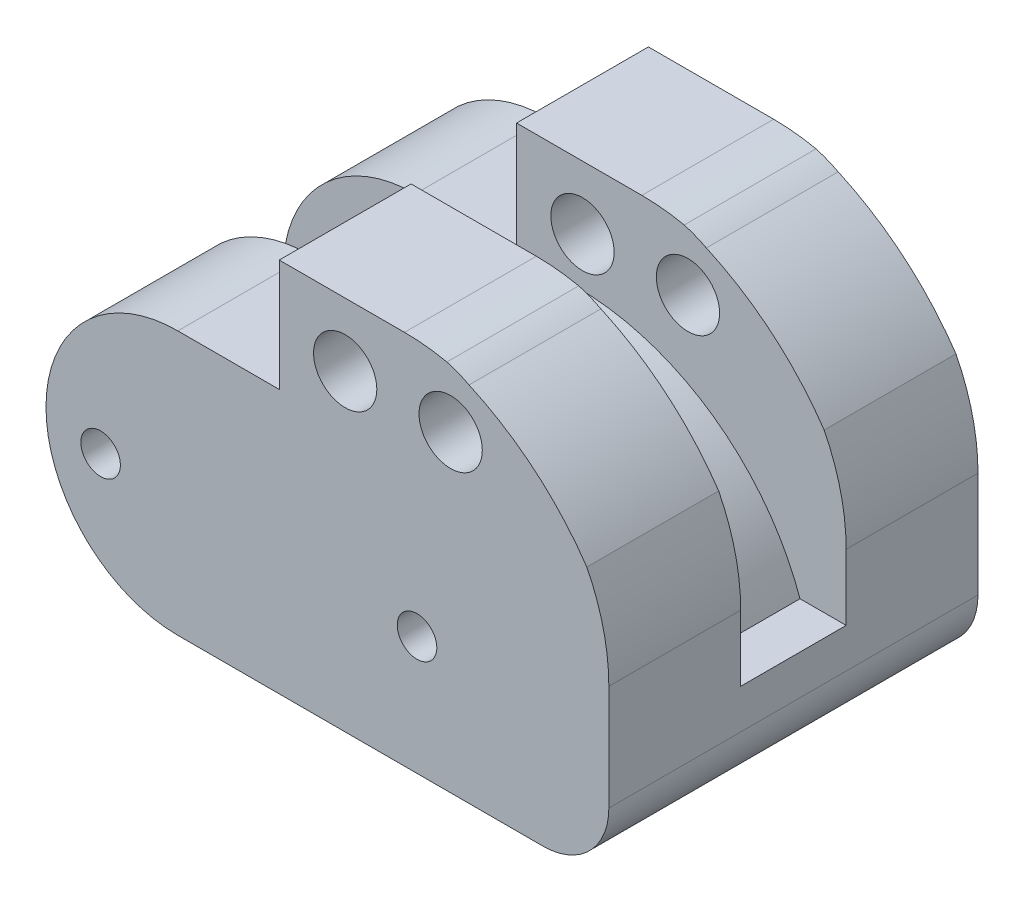
SolidWorks part; units mm, degrees
ref_plane "Alzado" through (0, 0, 0) normal (0, 0, 1) x (1, 0, 0)
ref_plane "Planta" through (0, 0, 0) normal (0, 1, 0) x (1, 0, 0)
ref_plane "Vista lateral" through (0, 0, 0) normal (1, 0, 0) x (0, 0, -1)
sketch "Croquis1" plane through (0, 0, 0) normal (0, 1, 0) x (1, 0, 0)
  line L1 (0, 0) -> (75, 0)
  line L2 (0, 0) -> (0, 28)
  line L3 (0, 28) -> (75, 28)
  line L4 (75, 0) -> (75, 28)
  dimension "D1" = 75
  dimension "D2" = 28
extrude "Saliente-Extruir2" add sketch "Croquis1" along normal blind 20
sketch "Croquis2" plane through (0, 20, 0) normal (0, 1, 0) x (1, 0, 0)
  line L0 (75, 0) -> (75, 28) construction
  line L1 (0, 0) -> (75, 0)
  line L2 (0, 0) -> (0, 10)
  line L3 (0, 10) -> (75, 10)
  line L4 (75, 0) -> (75, 10)
  line L6 (0, 28) -> (75, 28)
  line L7 (0, 28) -> (0, 18)
  line L8 (0, 18) -> (75, 18)
  line L9 (75, 28) -> (75, 18)
  dimension "D1" = 10
  dimension "D2" = 10
extrude "Saliente-Extruir3" add sketch "Croquis2" along normal blind 8.5
sketch "Croquis3" plane through (0, 0, 0) normal (0, 0, 1) x (1, 0, 0)
  line L1 (0, 28.5) -> (75, 28.5) construction
  line L2 (75, 28.5) -> (75, 0) construction
  circle A1 centre (63, 23.7) radius 2.4
  circle A2 centre (55, 23.7) radius 2.4
  dimension "D1" = 12
  dimension "D4" = 4.8
  dimension "D5" = 4.8
  dimension "D7" = 4.8
  dimension "D8" = 4.8
  dimension "D9" = 8
extrude "Cortar-Extruir1" cut sketch "Croquis3" against normal blind 28
sketch "Croquis5" plane through (0, 20, 0) normal (0, 1, 0) x (1, 0, 0)
  line L0 (0, 18) -> (75, 18) construction
  line L1 (75, 10) -> (71.5, 10)
  line L2 (75, 10) -> (75, 18)
  line L3 (75, 18) -> (71.5, 18)
  line L4 (71.5, 10) -> (71.5, 18)
  dimension "D1" = 3.5
extrude "Cortar-Extruir2" cut sketch "Croquis5" against normal blind 12
fillet "Redondeo1" radius 18 1 edges at (71.5, 20, -14)
sketch "Croquis7" plane through (0, 0, -18) normal (0, 0, 1) x (1, 0, 0)
  line L0 (55, 23.7) -> (50, 23.7) construction
  line L1 (50, 28.5) -> (50, 20)
  line L2 (0, 28.5) -> (75, 28.5) construction
  line L3 (0, 20) -> (54.5294, 20) construction
  line L4 (50, 28.5) -> (0, 28.5)
  line L5 (0, 28.5) -> (0, 20)
  line L6 (0, 20) -> (50, 20)
  circle A0 centre (55, 23.7) radius 2.4 construction
  dimension "D1" = 5
extrude "Cortar-Extruir3" cut sketch "Croquis7" against normal blind 9.5 and the other way blind 18.5
sketch "Croquis8" plane through (0, 20, 0) normal (0, 1, 0) x (1, 0, 0)
  line L0 (0, 27.5) -> (0, 0) construction
  line L1 (50, 10) -> (0, 10)
  line L2 (50, 10) -> (50, 19)
  line L3 (50, 19) -> (0, 19)
  line L4 (0, 10) -> (0, 19)
  dimension "D1" = 9
extrude "Cortar-Extruir4" cut sketch "Croquis8" against normal blind 20.5
fillet "Redondeo2" radius 10 2 edges at (0, 20, -5) (0, 20, -23.25)
sketch "Croquis9" plane through (0, 0, -28) normal (0, 0, -1) x (-1, 0, 0)
  line L0 (-75, 28.5) -> (-59.5, 28.5)
  line L1 (-75, 28.5) -> (0, 28.5) construction
  line L3 (-59.5, 28.5) -> (-59.5, 13) construction
  line L4 (-75, 28.5) -> (-75, 0) construction
  line L5 (-75, 28.5) -> (-75, 13)
  arc A0 (-75, 13) -> (-59.5, 28.5) centre (-59.5, 13) cw
  dimension "D1" = 15.5
fillet "Redondeo5" radius 10 1 edges at (0, 0, -5)
extrude "Cortar-Extruir6" cut sketch "Croquis9" against normal blind 28.5
sketch "Croquis10" plane through (0, 0, -28) normal (0, 0, -1) x (-1, 0, 0)
  line L0 (-60.4499, 9) -> (-36.4499, 9) construction
  line L1 (-75, 0) -> (-10, 0) construction
  line L2 (-36.4499, 9) -> (-12.4499, 9) construction
  line L3 (-75, 13) -> (-75, 0) construction
  circle A1 centre (-60.4499, 9) radius 1.5
  circle A2 centre (-36.4499, 9) radius 1.5
  circle A3 centre (-12.4499, 9) radius 1.5
  dimension "D3" = 3
  dimension "D4" = 3
  dimension "D5" = 3
  dimension "D6" = 9
  dimension "D7" = 14.5501
  dimension "D1" = 24
  dimension "D2" = 24
extrude "Cortar-Extruir7" cut sketch "Croquis10" against normal through all
fillet "Redondeo6" radius 10 1 edges at (50, 0, -14.5)
fillet "Redondeo7" radius 3 1 edges at (50, 20, -14)
fillet "Redondeo8" radius 5 1 edges at (75, 0, -14)
sketch "Croquis16" plane through (0, 0, -28) normal (0, 0, -1) x (-1, 0, 0)
  line L0 (-59.5, 28.5) -> (-59.5, 20) construction
  line L1 (-59.5, 20) -> (-73.3293, 20) construction
  line L2 (-59.5, 20) -> (-59.5, 19.34) construction
  line L3 (-59.5, 19.34) -> (-60.16, 19.34) construction
  line L4 (-60.16, 19.34) -> (-60.16, 20) construction
  line L5 (-73.3293, 20) -> (-69.3293, 20) construction
  line L6 (-69.3293, 20) -> (-73.3293, 20)
  arc A0 (-59.5, 28.5) -> (-75, 13) centre (-59.5, 13) ccw construction
  arc A1 (-59.5, 28.5) -> (-73.3293, 20) centre (-59.5, 13) ccw
  arc A2 (-69.3293, 20) -> (-59.5, 28.5) centre (-60.1647, 19.3353) cw
  circle A3 centre (-63, 23.7) radius 2.4 construction
  dimension "D3" = 9.1887
  dimension "D4" = 15.5
  dimension "D5" = 5.2047
  dimension "D1" = 0.66
  dimension "D2" = 0.66
  dimension "D6" = 4
extrude "Cortar-Extruir11" cut sketch "Croquis16" against normal through all contours L6 A2 A1
sketch "Croquis17" plane through (0, 0, -28) normal (0, 0, -1) x (-1, 0, 0)
  line L0 (-69.3293, 20) -> (-73.3293, 20)
  arc A0 (-73.3293, 20) -> (-62.7169, 28.1625) centre (-55.6181, 7.953) cw
  arc A1 (-69.3293, 20) -> (-62.7169, 28.1625) centre (-60.1647, 19.3353) cw
  line M1 (-69.3293, 20) -> (-73.3293, 20)
  arc M10 (-62.7169, 28.1625) -> (-69.3293, 20) centre (-60.1647, 19.3353) ccw
  dimension "D1" = 21.42
  dimension "D2" = 9.1887
extrude "Saliente-Extruir4" add sketch "Croquis17" against normal blind 10 contours A0 M1 M10
sketch "Croquis18" plane through (0, 0, 0) normal (0, 0, 1) x (1, 0, 0)
  line L0 (69.3293, 20) -> (73.3293, 20)
  arc A0 (69.3293, 20) -> (62.7169, 28.1625) centre (60.1647, 19.3353) ccw
  arc A1 (73.3293, 20) -> (62.7169, 28.1625) centre (55.6181, 7.953) ccw
  line M1 (73.3293, 20) -> (69.3293, 20)
  arc M2 (69.3293, 20) -> (62.7169, 28.1625) centre (60.1647, 19.3353) ccw
  dimension "D1" = 21.42
  dimension "D2" = 9.1887
extrude "Saliente-Extruir5" add sketch "Croquis18" against normal blind 10 contours A1 M1 M2
sketch "Croquis19" plane through (0, 0, -27.5) normal (0, 0, 1) x (1, 0, 0)
  line L0 (50, 20) -> (50, 28.5)
  line L1 (50, 28.5) -> (0, 28.5)
  line L2 (0, 28.5) -> (0, 10)
  line L3 (10, 20) -> (50, 20)
  arc A0 (0, 10) -> (10, 20) centre (10, 10) cw
extrude "Cortar-Extruir12" cut sketch "Croquis19" against normal blind 0.5
sketch "Croquis20" plane through (0, 0, -19) normal (0, 0, 1) x (1, 0, 0)
  line L0 (50, 20) -> (50, 10)
  line L1 (50, 20) -> (10, 20)
  line L2 (10, 0) -> (60, 0)
  arc A0 (60, 0) -> (50, 10) centre (60, 10) cw
  arc A1 (10, 20) -> (10, 0) centre (10, 10) ccw
  circle A2 centre (12.4499, 9) radius 1.5
  circle A3 centre (36.4499, 9) radius 1.5
  dimension "D1" = 3
  dimension "D2" = 3
extrude "Saliente-Extruir7" add sketch "Croquis20" along normal blind 1 contours A1 L2 A0 L0 L1 | A3 | A2
sketch "Croquis21" plane through (0, 0, 0) normal (0, 0, 1) x (1, 0, 0)
  line L0 (36.4499, 9) -> (36.4499, 10) construction
  line L1 (10, 0) -> (70, 0) construction
  line L2 (10, 20) -> (50, 20) construction
  line L3 (0, 10) -> (10, 10) construction
  line L4 (10, 20) -> (36.4499, 20)
  line L5 (10, 0) -> (36.4499, 0)
  arc A0 (36.4499, 0) -> (36.4499, 20) centre (36.4499, 10) cw
  arc A1 (10, 0) -> (10, 20) centre (10, 10) cw
  arc A2 (10, 20) -> (0, 10) centre (10, 10) ccw construction
  dimension "D1" = 10
extrude "Cortar-Extruir13" cut sketch "Croquis21" against normal through all
sketch "Croquis22" plane through (0, 0, 0) normal (0, 0, 1) x (1, 0, 0)
  arc A0 (36.4499, 0) -> (36.4499, 20) centre (46.4499, 10) cw
  arc A1 (36.4499, 0) -> (36.4499, 20) centre (36.4499, 10) cw
  dimension "D1" = 10
  dimension "D2" = 14.1421
extrude "Cortar-Extruir14" cut sketch "Croquis22" against normal through all
fillet "Redondeo9" radius 10 8 edges at (36.4499, 20, -5) (36.4499, 20, -23) (36.4499, 0, -5) (36.4499, 0, -23) (32.3077, 10, -10) (32.3077, 10, -18) (32.3077, 10, -28) (32.3077, 10, 0)
